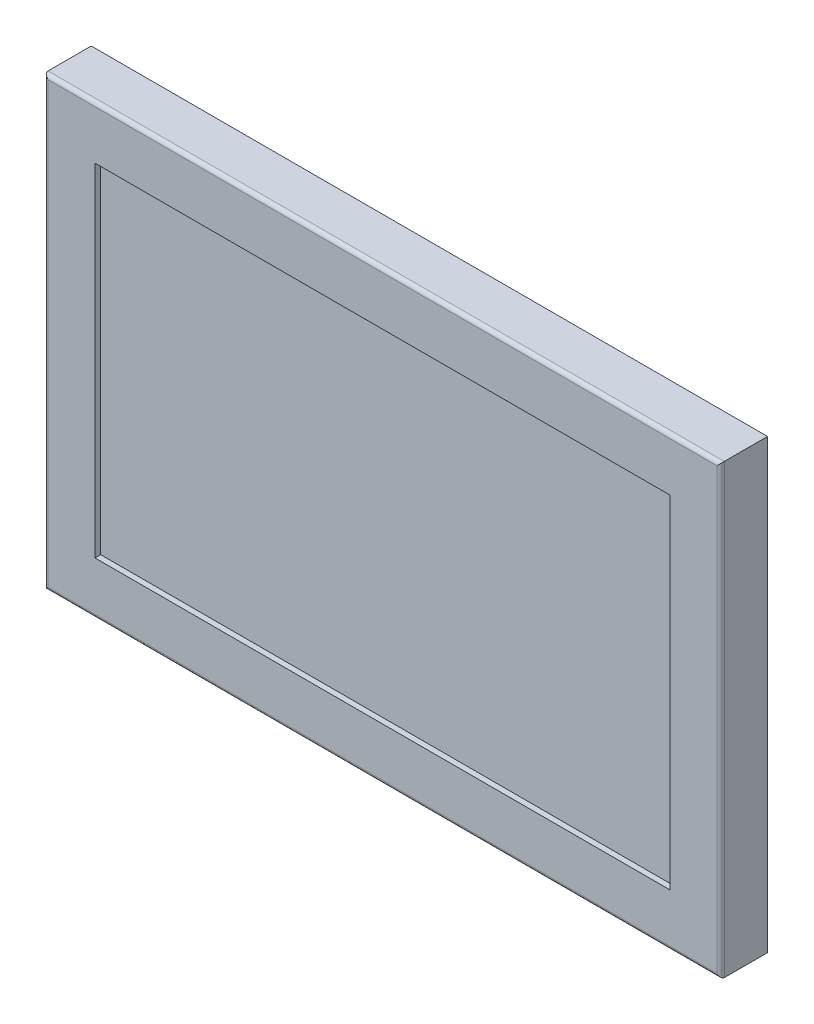
SolidWorks part; units mm, degrees
ref_plane "정면" through (0, 0, 0) normal (0, 0, 1) x (1, 0, 0)
ref_plane "윗면" through (0, 0, 0) normal (0, 1, 0) x (1, 0, 0)
ref_plane "우측면" through (0, 0, 0) normal (1, 0, 0) x (0, 0, -1)
sketch "스케치1" plane through (0, 0, 0) normal (0, 0, 1) x (1, 0, 0)
  line L1 (-90, 59.5) -> (90, 59.5)
  line L2 (-90, 59.5) -> (-90, -59.5)
  line L3 (-90, -59.5) -> (90, -59.5)
  line L4 (90, 59.5) -> (90, -59.5)
  line L5 (-90, 59.5) -> (90, -59.5) construction
  line L6 (-90, -59.5) -> (90, 59.5) construction
  point P0 (0, 0)
  dimension "D1" = 180
  dimension "D2" = 119
extrude "보스-돌출1" add sketch "스케치1" against normal blind 12.5
sketch "스케치2" plane through (0, 0, 0) normal (0, 0, 1) x (1, 0, 0)
  line L1 (-76.5, 45.5) -> (76.5, 45.5)
  line L2 (-76.5, 45.5) -> (-76.5, -45.5)
  line L3 (-76.5, -45.5) -> (76.5, -45.5)
  line L4 (76.5, 45.5) -> (76.5, -45.5)
  line L5 (-76.5, 45.5) -> (76.5, -45.5) construction
  line L6 (-76.5, -45.5) -> (76.5, 45.5) construction
  point P0 (0, 0)
  dimension "D1" = 91
  dimension "D2" = 153
extrude "컷-돌출1" cut sketch "스케치2" against normal blind 1.5
sketch "스케치3" plane through (0, 0, -12.5) normal (0, 0, -1) x (-1, 0, 0)
  line L0 (-90, 59.5) -> (90, 59.5) construction
  line L1 (-77.2, 51.5) -> (77.2, 51.5)
  line L2 (-77.2, 51.5) -> (-77.2, -43)
  line L3 (-77.2, -43) -> (77.2, -43)
  line L4 (77.2, 51.5) -> (77.2, -43)
  line L5 (-77.2, 51.5) -> (77.2, -43) construction
  line L6 (-77.2, -43) -> (77.2, 51.5) construction
  point P0 (0, 4.25)
  dimension "D1" = 94.5
  dimension "D2" = 154.4
  dimension "D3" = 8
extrude "보스-돌출2" add sketch "스케치3" along normal blind 31.5 separate body
sketch "스케치5" plane through (0, 0, 0) normal (0, 1, 0) x (1, 0, 0)
  line L0 (-90, 12.5) -> (-90, 0)
  line L1 (-90, 0) -> (-101.25, 0)
  line L2 (0, 0) -> (0, 43.5115) construction
  line L4 (91.2, 12.5) -> (90, 12.5)
  line L5 (-101.25, 0) -> (-101.25, 1.2)
  line L6 (-101.25, 1.2) -> (-91.2, 1.2)
  line L7 (-91.2, 1.2) -> (-91.2, 12.5)
  line L8 (-91.2, 12.5) -> (-90, 12.5)
  line L9 (91.2, 1.2) -> (91.2, 12.5)
  line L10 (101.25, 1.2) -> (91.2, 1.2)
  line L11 (101.25, 0) -> (101.25, 1.2)
  line L12 (90, 0) -> (101.25, 0)
  line L13 (90, 12.5) -> (90, 0)
  dimension "D1" = 1.2
  dimension "D2" = 1.2
  dimension "D3" = 202.5
extrude "보스-돌출3" [suppressed] add sketch "스케치5" along normal mid plane 119.2 separate body
sketch "스케치6" [suppressed] plane through (0, 0, 0) normal (0, 0, 1) x (1, 0, 0)
  circle A0 centre (-96.25, 49.6) radius 1.5
  circle A1 centre (-96.25, -49.6) radius 1.5
  circle A2 centre (96.25, 49.6) radius 1.5
  circle A3 centre (96.25, -49.6) radius 1.5
  dimension "D1" = 3
  dimension "D2" = 192.5
  dimension "D3" = 96.25
  dimension "D4" = 99.2
  dimension "D5" = 49.6
extrude "컷-돌출2" [suppressed] cut sketch "스케치6" against normal through all
sketch "스케치7" plane through (0, 51.5, 0) normal (0, 1, 0) x (1, 0, 0)
  line L0 (-77.2, 44) -> (-77.2, 12.5) construction
  line L1 (-77.2, 12.5) -> (77.2, 12.5) construction
  circle A0 centre (-40.2, 22.5) radius 1.6
  dimension "D1" = 3.2
  dimension "D2" = 37
  dimension "D3" = 10
extrude "보스-돌출4" add sketch "스케치7" along normal blind 3
pattern_linear "선형 패턴1" count 5 spacing 13.5 along (1, 0, 0) of "보스-돌출4"
sketch "스케치8" plane through (0, 51.5, 0) normal (0, 1, 0) x (1, 0, 0)
  line L0 (13.8, 22.5) -> (25.8, 22.5) construction
  circle A0 centre (25.8, 22.5) radius 1.75
  circle A1 centre (13.8, 22.5) radius 1.6 construction
  dimension "D2" = 3.5
  dimension "D1" = 12
extrude "컷-돌출3" cut sketch "스케치8" against normal blind 3
sketch "스케치9" plane through (0, 48.5, 0) normal (0, 1, 0) x (1, 0, 0)
  circle A0 centre (25.8, 22.5) radius 1.5
  dimension "D1" = 3
extrude "보스-돌출5" add sketch "스케치9" along normal blind 3
fillet "필렛1" radius 1.5 1 edges at (25.8, 51.5, -21)
hole_wizard "M4 나사 구멍1" positions "스케치11" profile "스케치10" tap size "M4" standard "KS"
sketch "스케치11" plane through (0, 0, -44) normal (0, 0, -1) x (-1, 0, 0)
  line L0 (77.2, 51.5) -> (-77.2, 51.5) construction
  point P0 (-37.5, 42)
  point P2 (37.5, 42)
  point P4 (-37.5, -33)
  point P6 (37.5, -33)
  dimension "D1" = 75
  dimension "D2" = 37.5
  dimension "D3" = 9.5
  dimension "D4" = 75
sketch "스케치10" plane through (37.5, 42, -44) normal (1, 0, 0) x (0, 1, 0)
  line L0 (0, 0) -> (0, 12.4914)
  line L1 (0, 12.4914) -> (1.65, 11.5)
  line L2 (1.65, 11.5) -> (1.65, 0)
  line L5 (1.65, 0) -> (0, 0)
  line L10 (0, 12.4914) -> (-1.65, 11.5) construction
  line L11 (0, -6.35) -> (0, 107.95) construction
  dimension "탭 드릴 지름" = 3.3
  dimension "탭 드릴 깊이" = 11.5
  dimension "드릴 각도" = 118
cosmetic thread "구멍 나사산1" parameters "D1"=8, "D2"=4
cosmetic thread "구멍 나사산2" parameters "D1"=8, "D2"=4
cosmetic thread "구멍 나사산3" parameters "D1"=8, "D2"=4
cosmetic thread "구멍 나사산4" parameters "D1"=8, "D2"=4
sketch "스케치12" plane through (0, -43, 0) normal (0, -1, 0) x (1, 0, 0)
  line L0 (-77.2, -44) -> (-77.2, -12.5) construction
  line L1 (-25.2, -28.75) -> (-35.2, -28.75)
  line L2 (-25.2, -28.75) -> (-25.2, -16.25)
  line L3 (-25.2, -16.25) -> (-35.2, -16.25)
  line L4 (-35.2, -28.75) -> (-35.2, -16.25)
  line L5 (-25.2, -28.75) -> (-35.2, -16.25) construction
  line L6 (-25.2, -16.25) -> (-35.2, -28.75) construction
  line L8 (77.2, -12.5) -> (-77.2, -12.5) construction
  point P0 (-30.2, -22.5)
  dimension "D1" = 10
  dimension "D2" = 12.5
  dimension "D3" = 47
  dimension "D4" = 10
extrude "컷-돌출4" cut sketch "스케치12" against normal blind 5
sketch "스케치13" plane through (0, -38, 0) normal (0, -1, 0) x (1, 0, 0)
  line L0 (-35.2, -16.25) -> (-35.2, -28.75) construction
  line L1 (-25.45, -26.5) -> (-34.95, -26.5)
  line L2 (-25.45, -26.5) -> (-25.45, -16.5)
  line L3 (-25.45, -16.5) -> (-34.95, -16.5)
  line L4 (-34.95, -26.5) -> (-34.95, -16.5)
  line L5 (-25.2, -28.75) -> (-25.2, -16.25) construction
  line L6 (-25.2, -16.25) -> (-35.2, -16.25) construction
  line L7 (-30.2, -26.5) -> (-30.2, -16.5) construction
  line L9 (77.2, -12.5) -> (-77.2, -12.5) construction
  circle A0 centre (-30.2, -22.5) radius 3
  circle A1 centre (-30.2, -22.5) radius 0.75
  dimension "D6" = 6
  dimension "D7" = 1.5
  dimension "D1" = 0.25
  dimension "D2" = 0.25
  dimension "D3" = 0.25
  dimension "D4" = 10
  dimension "D5" = 10
extrude "보스-돌출6" add sketch "스케치13" along normal blind 5 separate body contours L7 L1 L2 L3 A0 | L1 L7 A0 L3 L4 | L7 A1 | A1 L7 region at (-27.3581, -38, -21.0763) region at (-33.0419, -38, -21.0763) region at (-30.5183, -38, -22.5) region at (-29.8817, -38, -22.5)
fillet "필렛2" radius 0.75 1 edges at (-30.2, -43, -23.25)
sketch "스케치14" plane through (0, -43, 0) normal (0, -1, 0) x (1, 0, 0)
  line L0 (-77.2, -44) -> (-77.2, -12.5) construction
  line L1 (-30.2, -22.5) -> (-19.2, -22.5) construction
  circle A0 centre (-19.2, -22.5) radius 5
  dimension "D2" = 10
  dimension "D1" = 58
extrude "컷-돌출5" cut sketch "스케치14" against normal blind 2
sketch "스케치15" plane through (0, -41, 0) normal (0, -1, 0) x (1, 0, 0)
  circle A0 centre (-19.2, -22.5) radius 4.125
  circle A1 centre (-19.2, -22.5) radius 1.675
  dimension "D1" = 8.25
  dimension "D2" = 3.35
extrude "보스-돌출7" add sketch "스케치15" along normal blind 6.5 separate body
fillet "필렛3" radius 0.5 1 edges at (-15.075, -47.5, -22.5)
sketch "스케치16" plane through (0, -43, 0) normal (0, -1, 0) x (1, 0, 0)
  line L0 (-77.2, -44) -> (-77.2, -12.5) construction
  line L1 (-10.6, -22.5) -> (-19.2, -22.5) construction
  line L2 (14.9, -22.5) -> (-10.6, -22.5) construction
  line L3 (11.15, -28) -> (-6.85, -28)
  line L4 (9.65, -17) -> (-5.35, -17)
  line L5 (2.15, -22.5) -> (2.15, -28) construction
  line L6 (2.15, -22.5) -> (2.15, -17) construction
  line L7 (12.6243, -26.2236) -> (12.5824, -26)
  line L8 (-8.3243, -26.2236) -> (-8.2824, -26)
  line L9 (14.9, -26) -> (12.5824, -26)
  line L10 (14.9, -19) -> (11.2699, -19)
  line L11 (-10.6, -19) -> (-6.9699, -19)
  line L12 (-10.6, -26) -> (-8.2824, -26)
  line L13 (11.2699, -19) -> (11.1243, -18.2236)
  line L14 (-6.9699, -19) -> (-6.8243, -18.2236)
  arc A0 (14.9, -26) -> (14.9, -19) centre (14.9, -22.5) ccw
  arc A1 (-10.6, -19) -> (-10.6, -26) centre (-10.6, -22.5) ccw
  arc A2 (11.15, -28) -> (12.6243, -26.2236) centre (11.15, -26.5) ccw
  arc A3 (-6.85, -28) -> (-8.3243, -26.2236) centre (-6.85, -26.5) cw
  arc A4 (9.65, -17) -> (11.1243, -18.2236) centre (9.65, -18.5) cw
  arc A5 (-5.35, -17) -> (-6.8243, -18.2236) centre (-5.35, -18.5) ccw
  dimension "D1" = 32.5
  dimension "D3" = 7
  dimension "D8" = 1.5
  dimension "D2" = 66.6
  dimension "D4" = 18
  dimension "D5" = 15
  dimension "D6" = 5.5
  dimension "D7" = 5.5
extrude "컷-돌출6" cut sketch "스케치16" against normal blind 3
sketch "스케치17" plane through (0, -43, 0) normal (0, -1, 0) x (1, 0, 0)
  line L1 (56, -21) -> (24.5, -21) construction
  line L2 (52.25, -26.5) -> (28.25, -26.5)
  line L3 (50.75, -15.5) -> (29.75, -15.5)
  line L4 (40.25, -21) -> (40.25, -26.5) construction
  line L5 (40.25, -21) -> (40.25, -15.5) construction
  line L6 (53.7243, -24.7236) -> (53.6824, -24.5)
  line L7 (26.7757, -24.7236) -> (26.8176, -24.5)
  line L8 (56, -24.5) -> (53.6824, -24.5)
  line L9 (56, -17.5) -> (52.3699, -17.5)
  line L10 (24.5, -17.5) -> (28.1301, -17.5)
  line L11 (24.5, -24.5) -> (26.8176, -24.5)
  line L12 (52.3699, -17.5) -> (52.2243, -16.7236)
  line L13 (28.1301, -17.5) -> (28.2757, -16.7236)
  arc A0 (56, -24.5) -> (56, -17.5) centre (56, -21) ccw
  arc A1 (24.5, -17.5) -> (24.5, -24.5) centre (24.5, -21) ccw
  arc A2 (52.25, -26.5) -> (53.7243, -24.7236) centre (52.25, -25) ccw
  arc A3 (28.25, -26.5) -> (26.7757, -24.7236) centre (28.25, -25) cw
  arc A4 (50.75, -15.5) -> (52.2243, -16.7236) centre (50.75, -17) cw
  arc A5 (29.75, -15.5) -> (28.2757, -16.7236) centre (29.75, -17) ccw
  arc A6 (14.9, -26) -> (14.9, -19) centre (14.9, -22.5) ccw construction
  point P5 (18.4, -22.5)
  dimension "D2" = 7
  dimension "D7" = 1.5
  dimension "D1" = 38.5
  dimension "D3" = 24
  dimension "D4" = 21
  dimension "D5" = 5.5
  dimension "D6" = 5.5
  dimension "D8" = 1.5
  dimension "D9" = 9.6
extrude "컷-돌출7" cut sketch "스케치17" against normal blind 3
sketch "스케치18" plane through (0, -40, 0) normal (0, -1, 0) x (1, 0, 0)
  line L0 (14.9, -22.5) -> (-10.6, -22.5) construction
  line L1 (-11.7547, -24.5) -> (-9.4453, -24.5)
  line L2 (-9.4453, -24.5) -> (-8.2906, -22.5)
  line L3 (-8.2906, -22.5) -> (-9.4453, -20.5)
  line L4 (-9.4453, -20.5) -> (-11.7547, -20.5)
  line L5 (-11.7547, -20.5) -> (-12.9094, -22.5)
  line L6 (-12.9094, -22.5) -> (-11.7547, -24.5)
  line L7 (13.7453, -24.5) -> (16.0547, -24.5)
  line L8 (16.0547, -24.5) -> (17.2094, -22.5)
  line L9 (17.2094, -22.5) -> (16.0547, -20.5)
  line L10 (16.0547, -20.5) -> (13.7453, -20.5)
  line L11 (13.7453, -20.5) -> (12.5906, -22.5)
  line L12 (12.5906, -22.5) -> (13.7453, -24.5)
  line L13 (8.9, -26.5) -> (-4.6, -26.5)
  line L14 (7.9, -18.5) -> (-3.6, -18.5)
  line L15 (2.15, -22.5) -> (2.15, -18.5) construction
  line L16 (2.15, -22.5) -> (2.15, -26.5) construction
  line L17 (9.395, -25.9293) -> (8.395, -18.9293)
  line L18 (-5.095, -25.9293) -> (-4.095, -18.9293)
  line L19 (-4.095, -18.9293) -> (-26.2005, -19.9715)
  circle A0 centre (-10.6, -22.5) radius 2 construction
  circle A1 centre (14.9, -22.5) radius 2 construction
  arc A2 (8.9, -26.5) -> (9.395, -25.9293) centre (8.9, -26) ccw
  arc A3 (7.9, -18.5) -> (8.395, -18.9293) centre (7.9, -19) cw
  arc A4 (-3.6, -18.5) -> (-4.095, -18.9293) centre (-3.6, -19) ccw
  arc A5 (-4.6, -26.5) -> (-5.095, -25.9293) centre (-4.6, -26) cw
  dimension "D1" = 4
  dimension "D6" = 0.5
  dimension "D2" = 13.5
  dimension "D3" = 11.5
  dimension "D4" = 4
  dimension "D5" = 4
extrude "보스-돌출8" add sketch "스케치18" along normal blind 5 contours L11 L12 L7 L8 L9 L10 | A5 L13 A2 L17 A3 L14 A4 L18 | L5 L6 L1 L2 L3 L4 region at (-10.6, -40, -22.5) region at (14.9, -40, -22.5) region at (2.15, -40, -22.6105)
sketch "스케치19" plane through (0, -40, 0) normal (0, -1, 0) x (1, 0, 0)
  line L0 (24.5, -21) -> (56, -21) construction
  line L1 (26.8094, -21) -> (25.6547, -19)
  line L2 (25.6547, -19) -> (23.3453, -19)
  line L3 (23.3453, -19) -> (22.1906, -21)
  line L4 (22.1906, -21) -> (23.3453, -23)
  line L5 (23.3453, -23) -> (25.6547, -23)
  line L6 (25.6547, -23) -> (26.8094, -21)
  line L7 (53.6906, -21) -> (54.8453, -23)
  line L8 (54.8453, -23) -> (57.1547, -23)
  line L9 (57.1547, -23) -> (58.3094, -21)
  line L10 (58.3094, -21) -> (57.1547, -19)
  line L11 (57.1547, -19) -> (54.8453, -19)
  line L12 (54.8453, -19) -> (53.6906, -21)
  line L13 (40.25, -21) -> (40.25, -17) construction
  line L14 (40.25, -21) -> (40.25, -25) construction
  line L15 (29.75, -17) -> (50.75, -17)
  line L16 (29.75, -25) -> (50.75, -25)
  line L17 (29.25, -17.5) -> (29.25, -24.5)
  line L18 (51.25, -17.5) -> (51.25, -24.5)
  circle A0 centre (24.5, -21) radius 2 construction
  circle A1 centre (56, -21) radius 2 construction
  arc A2 (50.75, -17) -> (51.25, -17.5) centre (50.75, -17.5) cw
  arc A3 (50.75, -25) -> (51.25, -24.5) centre (50.75, -24.5) ccw
  arc A4 (29.75, -25) -> (29.25, -24.5) centre (29.75, -24.5) cw
  arc A5 (29.75, -17) -> (29.25, -17.5) centre (29.75, -17.5) ccw
  dimension "D1" = 4
  dimension "D5" = 0.5
  dimension "D2" = 21
  dimension "D3" = 4
  dimension "D4" = 4
extrude "보스-돌출9" add sketch "스케치19" along normal blind 5
sketch "스케치20" plane through (0, -43, 0) normal (0, -1, 0) x (1, 0, 0)
  line L1 (77.2, -12.5) -> (-77.2, -12.5) construction
  line L2 (-55.7, -17.5) -> (-55.7, -12.5)
  line L3 (-55.7, -12.5) -> (-63.7, -12.5)
  line L4 (-63.7, -12.5) -> (-63.7, -17.5)
  line L5 (-77.2, -44) -> (-77.2, -12.5) construction
  arc A0 (-63.7, -17.5) -> (-55.7, -17.5) centre (-59.7, -17.5) ccw
  dimension "D2" = 8
  dimension "D1" = 17.5
  dimension "D3" = 5
extrude "컷-돌출8" cut sketch "스케치20" against normal blind 3
sketch3d "3D스케치1"
  line L0 (-59.7, -43, -17.5) -> (-59.7, -78.4201, -17.5)
  line L2 (-59.7, -40, -17.5) -> (-59.7, -43, -17.5) construction
  line L3 (-59.7, -92.5622, -23.3579) -> (-59.7, -97.5635, -28.3591)
  line L4 (-59.7, -111.7056, -34.217) -> (-59.7, -122.7865, -34.217)
  arc A0 (-59.7, -97.5635, -28.3591) -> (-59.7, -111.7056, -34.217) centre (-59.7, -111.7056, -14.217) ccw
  arc A1 (-59.7, -78.4201, -17.5) -> (-59.7, -92.5622, -23.3579) centre (-59.7, -78.4201, -37.5) ccw
  point P10 (-59.7, -103.4213, -34.217)
  point P11 (-79.7, -111.7056, -14.217)
  point P14 (-59.7, -86.7044, -17.5)
  point P15 (-39.7, -78.4201, -37.5)
  dimension "D1" = 20
sketch "스케치21" plane through (0, -43, 0) normal (0, -1, 0) x (1, 0, 0)
  circle A0 centre (-59.7, -17.5) radius 2.25
  arc A1 (-63.7, -17.5) -> (-55.7, -17.5) centre (-59.7, -17.5) ccw construction
  dimension "D1" = 4.5
sweep "스윕1" add profiles "스케치21" path "3D스케치1"
fillet "필렛4" [suppressed] radius 3
fillet "필렛5" [suppressed] radius 3
fillet "필렛6" [suppressed] radius 1
fillet "필렛7" [suppressed] radius 0.5
fillet "필렛8" radius 1 4 edges at (0, -59.5, 0) (90, 0, 0) (0, 59.5, 0) (-90, 0, 0)
fillet "필렛9" [suppressed] radius 1
fillet "필렛10" [suppressed] radius 0.5
sketch "스케치22" plane through (0, -45, 0) normal (0, -1, 0) x (1, 0, 0)
  line L0 (24.5, -19) -> (24.5, -23) construction
  line L1 (25.6547, -19) -> (23.3453, -19) construction
  line L2 (23.3453, -23) -> (25.6547, -23) construction
  line L3 (56, -19) -> (56, -23) construction
  line L4 (57.1547, -19) -> (54.8453, -19) construction
  line L5 (54.8453, -23) -> (57.1547, -23) construction
  circle A0 centre (24.5, -21) radius 1
  circle A1 centre (56, -21) radius 1
  dimension "D1" = 2
extrude "컷-돌출9" cut sketch "스케치22" against normal blind 10
scale "Scale1" bodies to scale 102 scale about centroid uniform scaling yes scale factor 2
